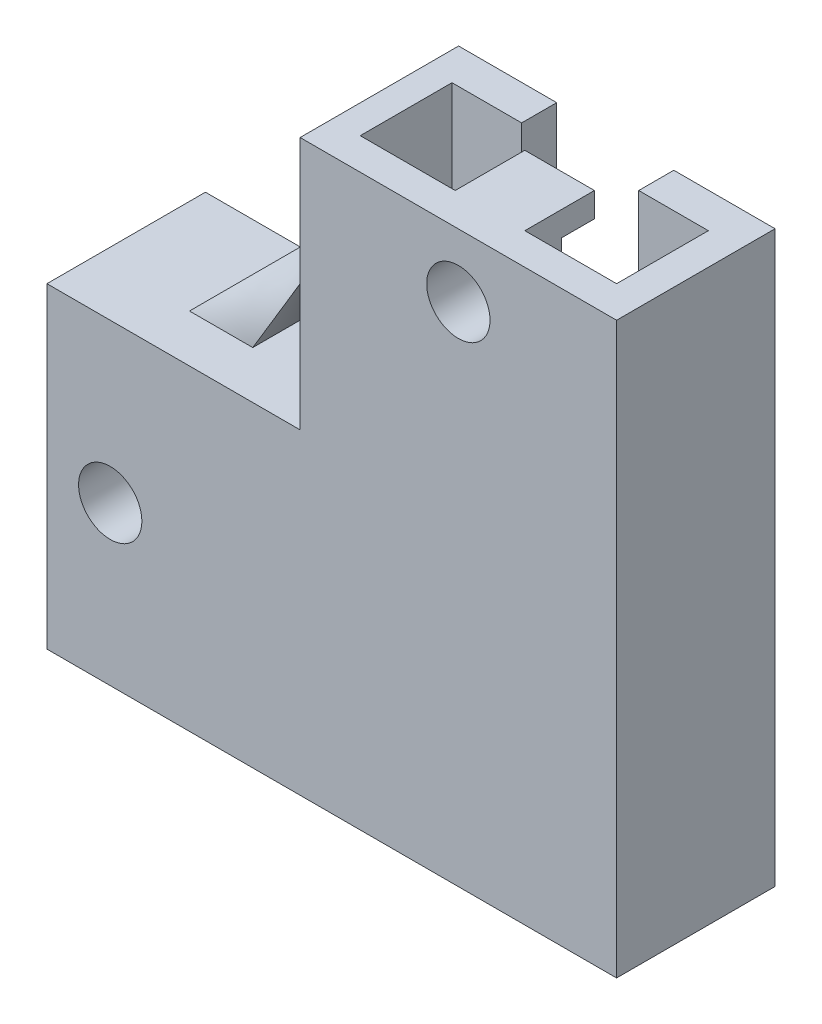
SolidWorks part; units mm, degrees
ref_plane "Front Plane" through (0, 0, 0) normal (0, 0, 1) x (1, 0, 0)
ref_plane "Top Plane" through (0, 0, 0) normal (0, 1, 0) x (1, 0, 0)
ref_plane "Right Plane" through (0, 0, 0) normal (1, 0, 0) x (0, 0, -1)
sketch "Sketch1" plane through (0, 0, 0) normal (0, 1, 0) x (1, 0, 0)
  line L1 (-12.5, -12.5) -> (12.5, -12.5)
  line L2 (-12.5, -12.5) -> (-12.5, 12.5)
  line L3 (-12.5, 12.5) -> (12.5, 12.5)
  line L4 (12.5, -12.5) -> (12.5, 12.5)
  line L5 (-12.5, -12.5) -> (12.5, 12.5) construction
  line L6 (-12.5, 12.5) -> (12.5, -12.5) construction
  point P0 (0, 0)
  dimension "D1" = 25
  dimension "D2" = 25
extrude "Boss-Extrude1" add sketch "Sketch1" along normal mid plane 45 contours L3 L4 L1 L2
sketch "Sketch3" plane through (0, -22.5, 0) normal (0, -1, 0) x (1, 0, 0)
  line L0 (-12.5, 12.5) -> (12.5, 12.5) construction
  line L2 (12.5, 12.5) -> (12.5, -12.5) construction
  line L4 (-12.5, 0) -> (-12.4984, 0) construction
  line L5 (-12.5, 12.5) -> (-12.5, -12.5) construction
  line L6 (12.5, 0) -> (12.4984, 0) construction
  line L8 (0, 10) -> (-2.75, 10)
  line L9 (-10.25, -10.25) -> (10, -10.25)
  line L10 (-10.25, -10.25) -> (-10.25, 10)
  line L11 (-10.25, 10) -> (10, 10)
  line L12 (10, -10.25) -> (10, 10)
  line L13 (-12.5, 12.5) -> (-12.5, -12.5) construction
  line L14 (-12.5, -12.5) -> (12.5, -12.5) construction
  line L15 (-2.75, 10) -> (-2.75, 4.5)
  line L16 (-2.75, 4.5) -> (2.75, 4.5)
  line L17 (2.75, 4.5) -> (2.75, 10)
  line L20 (-2.75, -10.25) -> (-2.75, -4.75)
  line L21 (-2.75, -4.75) -> (2.75, -4.75)
  line L22 (2.75, -4.75) -> (2.75, -10.25)
  line L24 (-10.25, 2.75) -> (-4.75, 2.75)
  line L25 (-4.75, 2.75) -> (-4.75, -2.75)
  line L26 (-4.75, -2.75) -> (-10.25, -2.75)
  line L28 (10, 2.75) -> (4.5, 2.75)
  line L29 (4.5, 2.75) -> (4.5, -2.75)
  line L30 (4.5, -2.75) -> (10, -2.75)
  point P17 (0, 0)
  dimension "D1" = 20.25
  dimension "D2" = 20.25
  dimension "D3" = 5.5
  dimension "D4" = 5.5
  dimension "D5" = 2.5
  dimension "D6" = 5.5
  dimension "D7" = 5.5
  dimension "D8" = 8
  dimension "D9" = 15.25
  dimension "D10" = 7.75
  dimension "D11" = 15.25
  dimension "D12" = 15.25
  dimension "D13" = 15.25
  dimension "D14" = 5.5
  dimension "D15" = 2.5
  dimension "D16" = 9.75
sketch "Sketch4" plane through (-12.5, 0, 0) normal (-1, 0, 0) x (0, 0, 1)
  line L0 (0, 22.5) -> (0, 0) construction
  line L1 (12.5, 22.5) -> (-12.5, 22.5) construction
  line L3 (-12.5, 22.5) -> (-12.5, -22.5) construction
  line L6 (12.5, 22.5) -> (12.5, -22.5) construction
  line L8 (-12.5, 0) -> (12.5, 0) construction
  line L10 (-12.5, 22.5) -> (12.5, 22.5)
  line L11 (-12.5, 22.5) -> (-12.5, -2.5)
  line L12 (-12.5, -2.5) -> (12.5, -2.5)
  line L13 (12.5, 22.5) -> (12.5, -2.5)
  dimension "D1" = 25
extrude "Boss-Extrude2" add sketch "Sketch4" along normal blind 20
sketch "Sketch5" plane through (-32.5, 0, 0) normal (-1, 0, 0) x (0, 0, 1)
  line L0 (-12.5, 22.5) -> (12.5, -2.5) construction
  line L1 (0, 20.125) -> (0, -0.125) construction
  line L2 (-10.125, -0.125) -> (10.125, -0.125)
  line L3 (-10.125, -0.125) -> (-10.125, 20.125)
  line L4 (-10.125, 20.125) -> (10.125, 20.125)
  line L5 (10.125, -0.125) -> (10.125, 20.125)
  line L6 (-10.125, -0.125) -> (10.125, 20.125) construction
  line L7 (-10.125, 20.125) -> (10.125, -0.125) construction
  line L8 (-10.125, 10) -> (10.125, 10) construction
  line L9 (0, 20.125) -> (-2.75, 20.125)
  line L10 (-2.75, 20.125) -> (-2.75, 14.625)
  line L11 (-2.75, 14.625) -> (2.75, 14.625)
  line L12 (2.75, 14.625) -> (2.75, 20.125)
  line L13 (-10.125, 10) -> (-10.125, 7.25)
  line L14 (-10.125, 7.25) -> (-4.625, 7.25)
  line L15 (-4.625, 7.25) -> (-4.625, 12.75)
  line L16 (-4.625, 12.75) -> (-10.125, 12.75)
  line L17 (0, -0.125) -> (-2.75, -0.125)
  line L18 (-2.75, -0.125) -> (-2.75, 5.375)
  line L19 (-2.75, 5.375) -> (2.75, 5.375)
  line L20 (2.75, 5.375) -> (2.75, -0.125)
  line L21 (10.125, 7.25) -> (4.625, 7.25)
  line L22 (4.625, 7.25) -> (4.625, 12.75)
  line L23 (4.625, 12.75) -> (10.125, 12.75)
  point P4 (0, 10)
  dimension "D1" = 20.25
  dimension "D2" = 5.5
  dimension "D3" = 5.5
  dimension "D4" = 5.5
  dimension "D5" = 5.5
  dimension "D6" = 5.5
  dimension "D7" = 5.5
  dimension "D8" = 5.5
  dimension "D9" = 5.5
  dimension "D10" = 2.75
  dimension "D11" = 2.75
  dimension "D12" = 2.75
extrude "Cut-Extrude2" cut sketch "Sketch3" against normal blind 42.5 contours L30 L29 L28 L12 L11 L17 L16 L15 L10 L24 L25 L26 L9 L20 L21 L22 region at (-0.1512, -22.5, -0.1512)
extrude "Cut-Extrude3" cut sketch "Sketch5" against normal blind 21.5 contours L22 L23 L5 L4 L12 L11 L10 L3 L16 L15 L14 L2 L18 L19 L20 L21 region at (-32.5, 10, 0)
sketch "Sketch6" plane through (0, 0, -12.5) normal (0, 0, -1) x (-1, 0, 0)
  line L0 (0, -22.5) -> (0, -12.5) construction
  line L1 (12.5, -22.5) -> (-12.5, -22.5) construction
  line L2 (22.5, 10) -> (32.5, 10) construction
  line L3 (32.5, 22.5) -> (32.5, -2.5) construction
  circle A0 centre (0, -12.5) radius 2.25
  circle A1 centre (22.5, 10) radius 2.25
  dimension "D1" = 4.5
  dimension "D2" = 4.5
  dimension "D3" = 10
  dimension "D4" = 10
extrude "Cut-Extrude4" cut sketch "Sketch6" against normal blind 10
sketch "Sketch8" plane through (0, 22.5, 0) normal (0, 1, 0) x (1, 0, 0)
  line L0 (12.5, -12.5) -> (12.5, 12.5) construction
  line L1 (-32.5, 12.5) -> (12.5, 12.5)
  line L2 (-32.5, 12.5) -> (-32.5, 0.0199)
  line L3 (-32.5, 0.0199) -> (12.5, 0.0199)
  line L4 (12.5, 12.5) -> (12.5, 0.0199)
  line L6 (-10, 12.5) -> (-10, -12.5) construction
  line L7 (-32.5, -12.5) -> (12.5, -12.5) construction
sketch "Sketch10" plane through (0, 0, 12.5) normal (0, 0, 1) x (1, 0, 0)
  line L0 (-32.5, 10) -> (12.5, 10) construction
  line L1 (-32.5, -2.5) -> (-32.5, 22.5) construction
  line L2 (12.5, 22.5) -> (12.5, -22.5) construction
  line L3 (0, -22.5) -> (0, 10) construction
  line L4 (-12.5, -22.5) -> (12.5, -22.5) construction
  circle A0 centre (-27.5, 10) radius 2.5
  circle A1 centre (0, -17.5) radius 2.5
  dimension "D1" = 5
  dimension "D2" = 5
  dimension "D3" = 5
  dimension "D4" = 5
extrude "Cut-Extrude7" cut sketch "Sketch10" against normal blind 10
sketch "Sketch11" plane through (0, 0, 4.5) normal (0, 0, -1) x (-1, 0, 0)
  line L1 (2.2226, -13.5502) -> (-2.3093, -13.6003)
  line L2 (-2.3093, -13.6003) -> (-4.5319, -17.55)
  line L3 (-4.5319, -17.55) -> (-2.2226, -21.4498)
  line L4 (-2.2226, -21.4498) -> (2.3093, -21.3997)
  line L5 (2.3093, -21.3997) -> (4.5319, -17.45)
  line L6 (4.5319, -17.45) -> (2.2226, -13.5502)
  line L7 (31.4124, 12.2878) -> (27.4749, 14.5321)
  line L8 (27.4749, 14.5321) -> (23.5625, 12.2443)
  line L9 (23.5625, 12.2443) -> (23.5876, 7.7122)
  line L10 (23.5876, 7.7122) -> (27.5251, 5.4679)
  line L11 (27.5251, 5.4679) -> (31.4375, 7.7557)
  line L12 (31.4375, 7.7557) -> (31.4124, 12.2878)
  circle A0 centre (0, -17.5) radius 3.925 construction
  circle A1 centre (27.5, 10) radius 3.925 construction
  dimension "D1" = 7.85
  dimension "D2" = 7.85
extrude "Cut-Extrude8" cut sketch "Sketch11" against normal blind 2.6
extrude "Cut-Extrude9" cut sketch "Sketch8" against normal blind 50
sketch "Sketch15" plane through (0, -2.5, 0) normal (0, -1, 0) x (1, 0, 0)
  line L0 (-32.5, 12.5) -> (-12.5, -0.0199) construction
  line L1 (-25, 3.74) -> (-20, 3.74)
  line L2 (-25, 3.74) -> (-25, 8.74)
  line L3 (-25, 8.74) -> (-20, 8.74)
  line L4 (-20, 3.74) -> (-20, 8.74)
  line L5 (-25, 3.74) -> (-20, 8.74) construction
  line L6 (-25, 8.74) -> (-20, 3.74) construction
  point P0 (-22.5, 6.24)
  dimension "D1" = 5
  dimension "D2" = 5
sketch "Sketch16" plane through (-12.5, 0, 0) normal (-1, 0, 0) x (0, 0, 1)
  line L0 (-0.0199, -2.5) -> (12.5, -22.5) construction
  line L2 (3.74, -15) -> (8.74, -15)
  line L3 (3.74, -15) -> (3.74, -10)
  line L4 (3.74, -10) -> (8.74, -10)
  line L5 (8.74, -15) -> (8.74, -10)
  line L6 (3.74, -15) -> (8.74, -10) construction
  line L7 (3.74, -10) -> (8.74, -15) construction
  point P4 (6.24, -12.5)
  dimension "D1" = 5
  dimension "D2" = 5
sketch "Sketch17" plane through (0, -2.5, 0) normal (0, -1, 0) x (1, 0, 0)
loft "Loft1" add profiles "Sketch15", "Sketch16" connector at (-20, -2.5, 8.74) connector at (-12.5, -15, 8.74)
mirror "Mirror1" about plane through (0, 22.5, 0) normal (0, -1, 0) of bodies 112
delete or keep bodies "Body-Delete1" type delete bodies bodies 112
